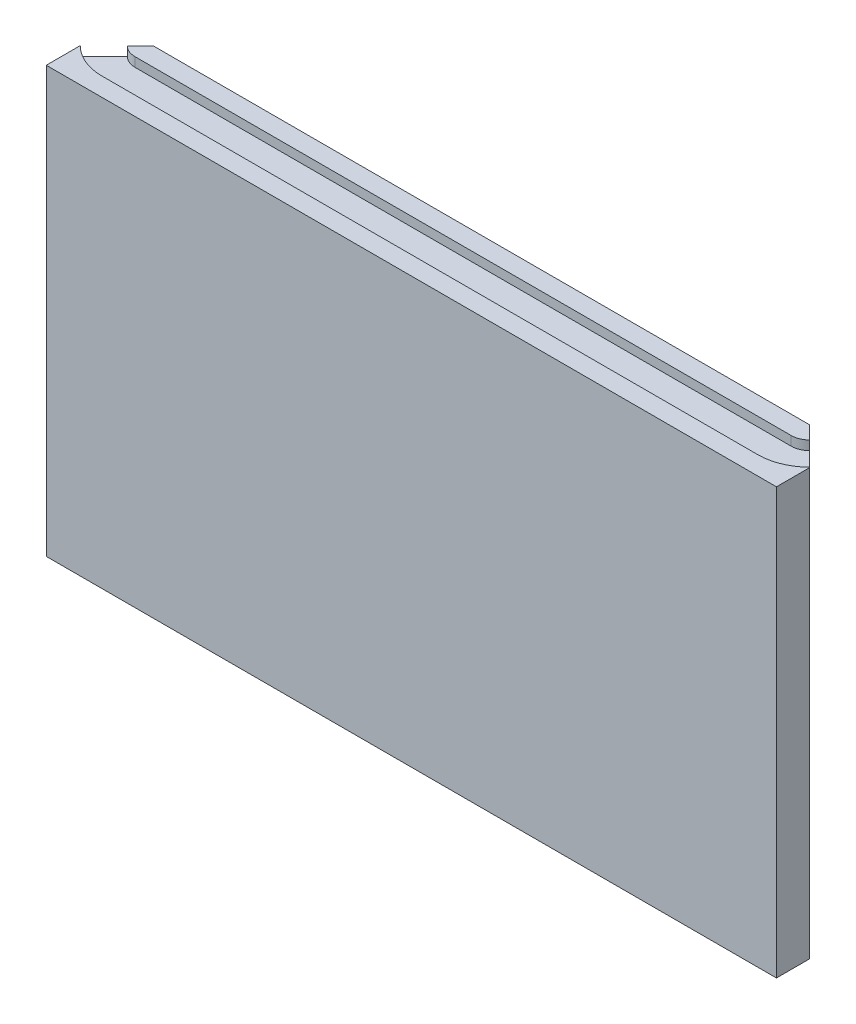
SolidWorks part; units mm, degrees
ref_plane "Front Plane" through (0, 0, 0) normal (0, 0, 1) x (1, 0, 0)
ref_plane "Top Plane" through (0, 0, 0) normal (0, 1, 0) x (1, 0, 0)
ref_plane "Right Plane" through (0, 0, 0) normal (1, 0, 0) x (0, 0, -1)
sketch "Sketch1" plane through (0, 0, 0) normal (0, 0, 1) x (1, 0, 0)
  line L2 (-98.7, -57.5) -> (-98.7, 57.5)
  line L5 (-98.7, 57.5) -> (98.7, 57.5)
  line L9 (98.7, 57.5) -> (98.7, -57.5)
  line L14 (98.7, -57.5) -> (-98.7, -57.5)
  dimension "D1" = 115
  dimension "D2" = 57.5
extrude "Boss-Extrude1" add sketch "Sketch1" along normal blind 9
sketch "Sketch2" plane through (0, 57.5, 0) normal (0, 1, 0) x (1, 0, 0)
  line L0 (-88.7, 10) -> (88.7, 10)
  line L1 (98.7, 0) -> (-98.7, 0) construction
  line L2 (-98.7, 0) -> (-88.7, 10)
  line L3 (98.7, 0) -> (88.7, 10)
  line L5 (-98.7, 0) -> (98.7, 0)
  dimension "D1" = 10
extrude "Boss-Extrude2" add sketch "Sketch2" against normal blind 10
sketch "Sketch3" plane through (0, 0, 9) normal (0, 0, 1) x (1, 0, 0)
  line L0 (-98.7, -57.5) -> (98.7, -57.5) construction
  line L1 (-80.7, 45.5) -> (-40.7, 45.5)
  line L2 (-86.7, 39.5) -> (-86.7, -39.5)
  line L3 (-80.7, -45.5) -> (-40.7, -45.5)
  line L4 (-34.7, 39.5) -> (-34.7, -39.5)
  line L6 (98.7, 57.5) -> (-98.7, 57.5) construction
  line L7 (-98.7, 57.5) -> (-98.7, -57.5) construction
  line L8 (-26.7, 19.985) -> (-26.7, 32.685) construction
  arc A0 (-86.7, -39.5) -> (-80.7, -45.5) centre (-80.7, -39.5) ccw
  arc A1 (-40.7, -45.5) -> (-34.7, -39.5) centre (-40.7, -39.5) ccw
  arc A2 (-40.7, 45.5) -> (-34.7, 39.5) centre (-40.7, 39.5) cw
  arc A3 (-80.7, 45.5) -> (-86.7, 39.5) centre (-80.7, 39.5) ccw
  dimension "D2" = 6
  dimension "D1" = 12
  dimension "D3" = 12
  dimension "D4" = 12
  dimension "D5" = 8
extrude "Cut-Extrude1" [suppressed] cut sketch "Sketch3" against normal up to surface (9 mm away) up to face at (0, -5, 0)
sketch "Sketch4" plane through (0, 0, 9) normal (0, 0, 1) x (1, 0, 0)
  line L8 (-94.7, 39.5) -> (-94.7, -39.5)
  line L9 (-80.7, -53.5) -> (-40.7, -53.5)
  line L10 (-26.7, -39.5) -> (-26.7, 39.5)
  line L11 (-40.7, 53.5) -> (-80.7, 53.5)
  line L12 (-94.7, 39.5) -> (-94.7, -39.5)
  line L13 (-80.7, -53.5) -> (-40.7, -53.5)
  line L14 (-26.7, -39.5) -> (-26.7, 39.5)
  line L15 (-40.7, 53.5) -> (-80.7, 53.5)
  arc A8 (-94.7, -39.5) -> (-80.7, -53.5) centre (-80.7, -39.5) ccw
  arc A9 (-40.7, -53.5) -> (-26.7, -39.5) centre (-40.7, -39.5) ccw
  arc A10 (-26.7, 39.5) -> (-40.7, 53.5) centre (-40.7, 39.5) ccw
  arc A11 (-80.7, 53.5) -> (-94.7, 39.5) centre (-80.7, 39.5) ccw
  arc A12 (-94.7, -39.5) -> (-80.7, -53.5) centre (-80.7, -39.5) ccw
  arc A13 (-40.7, -53.5) -> (-26.7, -39.5) centre (-40.7, -39.5) ccw
  arc A14 (-26.7, 39.5) -> (-40.7, 53.5) centre (-40.7, 39.5) ccw
  arc A15 (-80.7, 53.5) -> (-94.7, 39.5) centre (-80.7, 39.5) ccw
  dimension "D1" = 8
extrude "Cut-Extrude2" [suppressed] cut sketch "Sketch4" against normal blind 6
mirror "Mirror1" [suppressed] about plane through (0, 0, 0) normal (1, 0, 0)
sketch "Sketch5" plane through (0, 57.5, 0) normal (0, 1, 0) x (1, 0, 0)
  line L0 (-88.7, 5) -> (88.7, 5)
  line L1 (-88.7, 10) -> (-98.7, 0) construction
  line L2 (98.7, 0) -> (88.7, 10) construction
  line L3 (88.7, 10) -> (-88.7, 10) construction
  line L4 (-88.7, -4) -> (88.7, -4)
  line L11 (-98.5995, 0.1005) -> (-92.2355, 6.4645)
  line L12 (92.2355, 6.4645) -> (98.5995, 0.1005)
  arc A0 (-88.7, 5) -> (-92.2355, 6.4645) centre (-88.7, 10) cw
  arc A1 (88.7, 5) -> (92.2355, 6.4645) centre (88.7, 10) ccw
  arc A2 (88.7, -4) -> (98.5995, 0.1005) centre (88.7, 10) ccw
  arc A3 (-88.7, -4) -> (-98.5995, 0.1005) centre (-88.7, 10) cw
  dimension "D1" = 5
  dimension "D2" = 9
extrude "Cut-Extrude3" cut sketch "Sketch5" against normal blind 2.5
mirror "Mirror2" about plane through (0, 0, 0) normal (0, 1, 0) of "Cut-Extrude3", "Boss-Extrude2"
